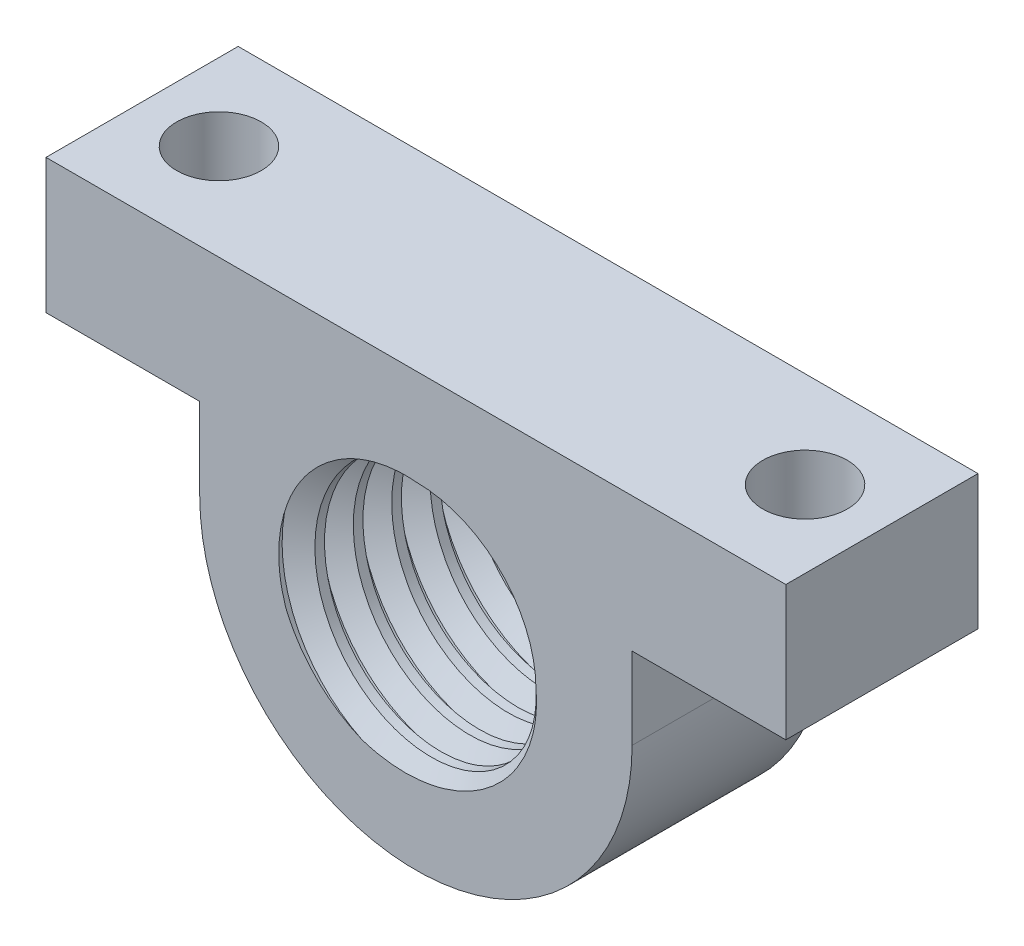
SolidWorks part; units mm, degrees
ref_plane "Ebene vorne" through (0, 0, 0) normal (0, 0, 1) x (1, 0, 0)
ref_plane "Ebene oben" through (0, 0, 0) normal (0, 1, 0) x (1, 0, 0)
ref_plane "Ebene rechts" through (0, 0, 0) normal (1, 0, 0) x (0, 0, -1)
sketch "Skizze1" plane through (0, 0, 0) normal (0, 0, 1) x (1, 0, 0)
  line L0 (-11.25, 0) -> (-11.25, 11.25)
  line L1 (0, 11.25) -> (-11.25, 11.25) construction
  line L2 (11.25, 0) -> (11.25, 11.25)
  line L3 (11.25, 11.25) -> (0, 11.25)
  line L4 (0, 11.25) -> (-11.25, 11.25)
  circle A0 centre (0, 0) radius 6.25
  arc A1 (-11.25, 0) -> (11.25, 0) centre (0, 0) ccw
  dimension "D1" = 12.5
  dimension "D2" = 5
extrude "Aufsatz-Linear austragen1" add sketch "Skizze1" along normal blind 10
sketch "Skizze2" plane through (0, 11.25, 0) normal (0, 1, 0) x (1, 0, 0)
  line L0 (11.25, 0) -> (19.25, 0)
  line L1 (19.25, 0) -> (19.25, -10)
  line L2 (19.25, -10) -> (11.25, -10)
  line L3 (11.25, -10) -> (11.25, 0) construction
  line L4 (11.25, 0) -> (11.25, -10)
  line L5 (0, 0) -> (0, -5.796) construction
  line L6 (-11.25, 0) -> (-11.25, -10)
  line L7 (-19.25, -10) -> (-11.25, -10)
  line L8 (-19.25, 0) -> (-19.25, -10)
  line L9 (-11.25, 0) -> (-19.25, 0)
  dimension "D1" = 8
extrude "Aufsatz-Linear austragen2" add sketch "Skizze2" against normal blind 7
thread "Gewinde1" pitch 2 method cut profile "Gewindeprofil1" start angle 0, offset 2, length 15, pitch 2, diameter 12.5
ref_plane "Ebene1" through (6.25, 0, -2) normal (0, -1, 0) x (1, 0, 0)
sketch "Gewindeprofil1" plane through (6.25, 0, -2) normal (0, -1, 0) x (1, 0, 0)
  line L0 (0, 0) -> (0, 2) construction
  line L1 (0, 0) -> (1.0825, 0.625)
  line L2 (1.0825, 0.625) -> (1.0825, 0.875)
  line L3 (1.0825, 0.875) -> (0, 1.5)
  line L4 (1.0825, 0.75) -> (0, 0.75) construction
  line L11 (0, 0) -> (0, 1.5)
  point P2 (0, 0)
  dimension "Pitch" = 2
  dimension "Profile_Angle" = 60
  dimension "Profile_Land" = 0.25
  dimension "Profile_Height" = 1.0825
sketch "Skizze5" plane through (0, 4.25, 0) normal (0, -1, 0) x (1, 0, 0)
  line L0 (15.25, 10) -> (15.25, 0) construction
  line L1 (11.25, 10) -> (19.25, 10) construction
  line L2 (19.25, 0) -> (11.25, 0) construction
  line L3 (0, 0) -> (0, 4.322) construction
  line L4 (-11.25, 0) -> (11.25, 0) construction
  circle A0 centre (15.25, 5) radius 2.2
  circle A1 centre (-15.25, 5) radius 2.2
  dimension "D1" = 4.4
extrude "Schnitt-Linear austragen1" cut sketch "Skizze5" against normal through all
